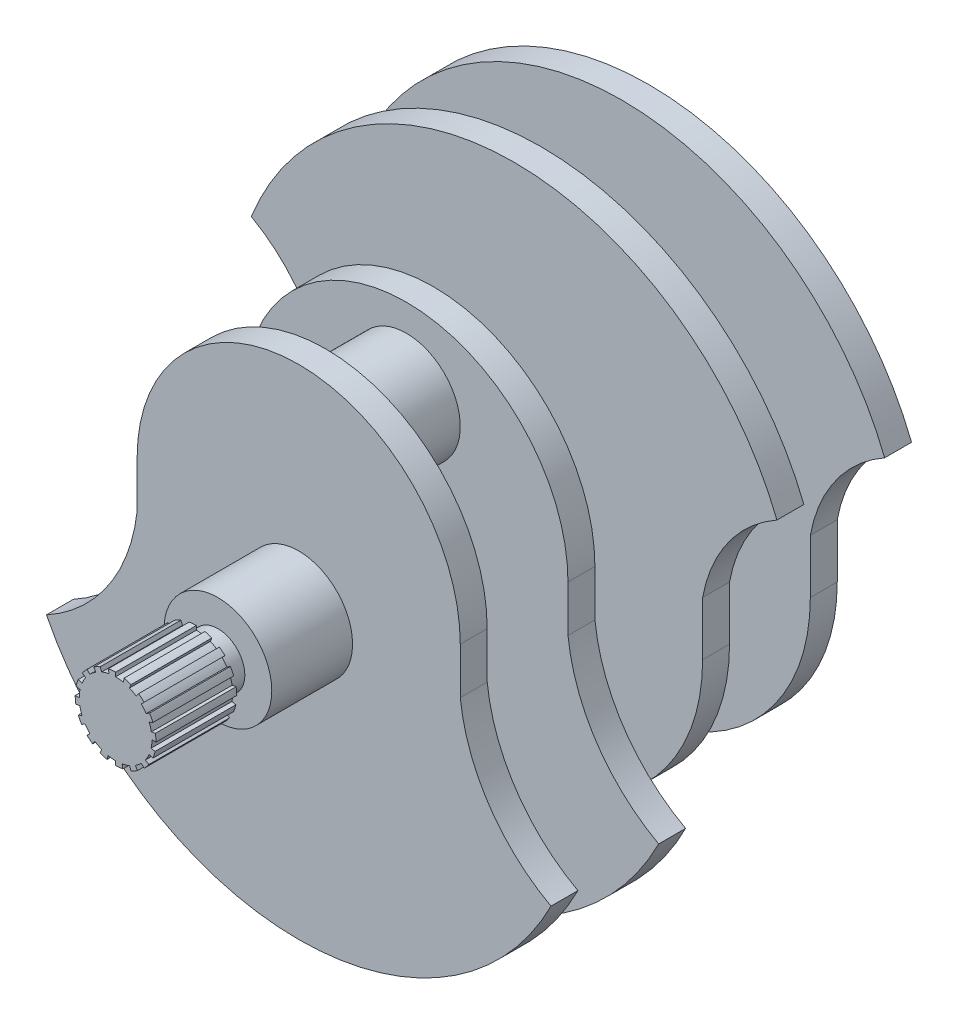
SolidWorks part; units mm, degrees
material "AISI 4340 Steel, normalized"
ref_plane "Front Plane" through (0, 0, 0) normal (0, 0, 1) x (1, 0, 0)
ref_plane "Top Plane" through (0, 0, 0) normal (0, 1, 0) x (1, 0, 0)
ref_plane "Right Plane" through (0, 0, 0) normal (1, 0, 0) x (0, 0, -1)
sketch "Sketch1" plane through (0, 0, 0) normal (0, 0, 1) x (1, 0, 0)
  circle A0 centre (0, 0) radius 20
  dimension "D1" = 20
extrude "Boss-Extrude1" add sketch "Sketch1" along normal blind 30
sketch "Sketch2" plane through (0, 0, 30) normal (0, 0, 1) x (1, 0, 0)
  circle A0 centre (0, 0) radius 10
  dimension "D1" = 10
extrude "Boss-Extrude2" add sketch "Sketch2" along normal blind 8
sketch "Sketch3" plane through (0, 0, 38) normal (0, 0, 1) x (1, 0, 0)
  circle A0 centre (0, 0) radius 15
  dimension "D1" = 15
extrude "Boss-Extrude3" add sketch "Sketch3" along normal blind 30
sketch "Sketch5" plane through (0, 0, 68) normal (0, 0, 1) x (1, 0, 0)
  line L0 (0, 15) -> (0, 13.5)
  line L1 (2.8421, 13.1974) -> (3.1579, 14.6638)
  circle A0 centre (0, 0) radius 15 construction
  arc A1 (0, 13.5) -> (2.8421, 13.1974) centre (0, 0) cw
  arc A2 (3.1579, 14.6638) -> (0, 15) centre (0, 0) ccw
  circle A3 centre (0, 0) radius 15
  point P8 (0, 14.25)
  circle M6 centre (0, 0) radius 15
  dimension "D1" = 13.5
  dimension "D2" = 3
extrude "Cut-Extrude1" cut sketch "Sketch5" against normal up to next contours L0 A1 L1 M6 region at (1.507, 14.1564, 68)
pattern_circular "CirPattern1" count 16 over 360 about axis through (0, 0, 68) along (0, 0, 1) of "Cut-Extrude1"
sketch "Sketch8" plane through (0, 0, 0) normal (0, 0, -1) x (-1, 0, 0)
  line L0 (-60, 20) -> (-60, 2.7836)
  line L1 (60, 20) -> (60, 2.7836)
  arc A0 (60, 20) -> (-60, 20) centre (0, 20) ccw
  arc A5 (-93.6849, -47.4146) -> (93.6849, -47.4146) centre (0, 0) ccw
  arc A6 (-60, 2.7836) -> (-93.6849, -47.4146) centre (-125, 10) cw
  arc A7 (60, 2.7836) -> (93.6849, -47.4146) centre (125, 10) ccw
  dimension "D1" = 60
  dimension "D2" = 105
  dimension "D3" = 20
  dimension "D5" = 10
  dimension "D6" = 125
extrude "Boss-Extrude5" add sketch "Sketch8" along normal blind 10
sketch "Sketch9" plane through (0, 0, -10) normal (0, 0, -1) x (-1, 0, 0)
  circle A0 centre (0, 50) radius 20
  dimension "D2" = 20
  dimension "D1" = 50
extrude "Boss-Extrude6" add sketch "Sketch9" along normal blind 30
ref_plane "Plane4" through (0, 0, -80) normal (0, 0, -1) x (-1, 0, 0)
sketch "Sketch10" plane through (0, 0, -40) normal (0, 0, -1) x (-1, 0, 0)
  line L0 (-70, -20) -> (-70, 0)
  line L1 (70, -20) -> (70, 0)
  arc A0 (-70, -20) -> (70, -20) centre (0, -20) ccw
  arc A1 (-70, 0) -> (-97.598, 38.7251) centre (-125, -10) ccw
  arc A2 (70, 0) -> (97.598, 38.7251) centre (125, -10) cw
  arc A3 (-97.598, 38.7251) -> (97.598, 38.7251) centre (0, 0) cw
  point P1 (0, 0)
  point P10 (0, 0)
  dimension "D1" = 70
  dimension "D3" = 105
  dimension "D2" = 20
  dimension "D4" = 125
  dimension "D5" = 10
extrude "Boss-Extrude7" add sketch "Sketch10" along normal blind 10 from surface starting at plane "Plane4"
ref_plane "Plane3" through (0, 0, -120) normal (0, 0, -1) x (-1, 0, 0)
sketch "Sketch12" plane through (0, 0, -120) normal (0, 0, -1) x (-1, 0, 0)
  line L2 (70, -20) -> (70, 0)
  line L3 (70, -20) -> (70, 0)
  line L4 (-70, 0) -> (-70, -20)
  line L5 (-70, 0) -> (-70, -20)
  arc A12 (-70, -20) -> (70, -20) centre (0, -20) ccw
  arc A13 (97.598, 38.7251) -> (70, 0) centre (125, -10) ccw
  arc A14 (97.598, 38.7251) -> (-97.598, 38.7251) centre (0, 0) ccw
  arc A15 (-70, 0) -> (-97.598, 38.7251) centre (-125, -10) ccw
  arc A16 (-70, -20) -> (70, -20) centre (0, -20) ccw
  arc A17 (97.598, 38.7251) -> (70, 0) centre (125, -10) ccw
  arc A18 (97.598, 38.7251) -> (-97.598, 38.7251) centre (0, 0) ccw
  arc A19 (-70, 0) -> (-97.598, 38.7251) centre (-125, -10) ccw
  dimension "D1" = 0
extrude "Boss-Extrude8" add sketch "Sketch12" along normal blind 10
sketch "Sketch14" plane through (0, 0, -90) normal (0, 0, -1) x (-1, 0, 0)
  circle A0 centre (0, -50) radius 20
  dimension "D2" = 20
  dimension "D1" = 50
extrude "Boss-Extrude9" add sketch "Sketch14" along normal up to next
sketch "Sketch15" plane through (0, 0, -130) normal (0, 0, -1) x (-1, 0, 0)
  circle A1 centre (0, 0) radius 20
  circle A2 centre (0, 0) radius 20
  dimension "D1" = 0
extrude "Boss-Extrude10" add sketch "Sketch15" along normal blind 30
sketch "Sketch16" plane through (0, 0, -160) normal (0, 0, -1) x (-1, 0, 0)
  circle A1 centre (0, 0) radius 10
  circle A2 centre (0, 0) radius 10
  dimension "D1" = 0
extrude "Boss-Extrude11" add sketch "Sketch16" along normal blind 8
sketch "Sketch18" plane through (0, 0, -40) normal (0, 0, -1) x (-1, 0, 0)
  line L2 (-60, 20) -> (-60, 2.7836)
  line L3 (-60, 20) -> (-60, 2.7836)
  line L4 (60, 2.7836) -> (60, 20)
  line L5 (60, 2.7836) -> (60, 20)
  arc A4 (60, 20) -> (-60, 20) centre (0, 20) ccw
  arc A5 (-93.6849, -47.4146) -> (-60, 2.7836) centre (-125, 10) ccw
  arc A6 (-93.6849, -47.4146) -> (93.6849, -47.4146) centre (0, 0) ccw
  arc A7 (60, 2.7836) -> (93.6849, -47.4146) centre (125, 10) ccw
  arc A8 (60, 20) -> (-60, 20) centre (0, 20) ccw
  arc A9 (-93.6849, -47.4146) -> (-60, 2.7836) centre (-125, 10) ccw
  arc A10 (-93.6849, -47.4146) -> (93.6849, -47.4146) centre (0, 0) ccw
  arc A11 (60, 2.7836) -> (93.6849, -47.4146) centre (125, 10) ccw
  dimension "D1" = 0
extrude "Boss-Extrude12" add sketch "Sketch18" along normal blind 10
sketch "Sketch19" plane through (0, 0, -50) normal (0, 0, -1) x (-1, 0, 0)
  circle A1 centre (0, 0) radius 20
  circle A2 centre (0, 0) radius 20
  dimension "D1" = 0
extrude "Boss-Extrude13" add sketch "Sketch19" along normal blind 30
equation "\"Crank Radius\"= 50mm"
equation "\"D1@Sketch9\"=\"Crank Radius\""
equation "\"D1@Sketch14\"=\"Crank Radius\""
